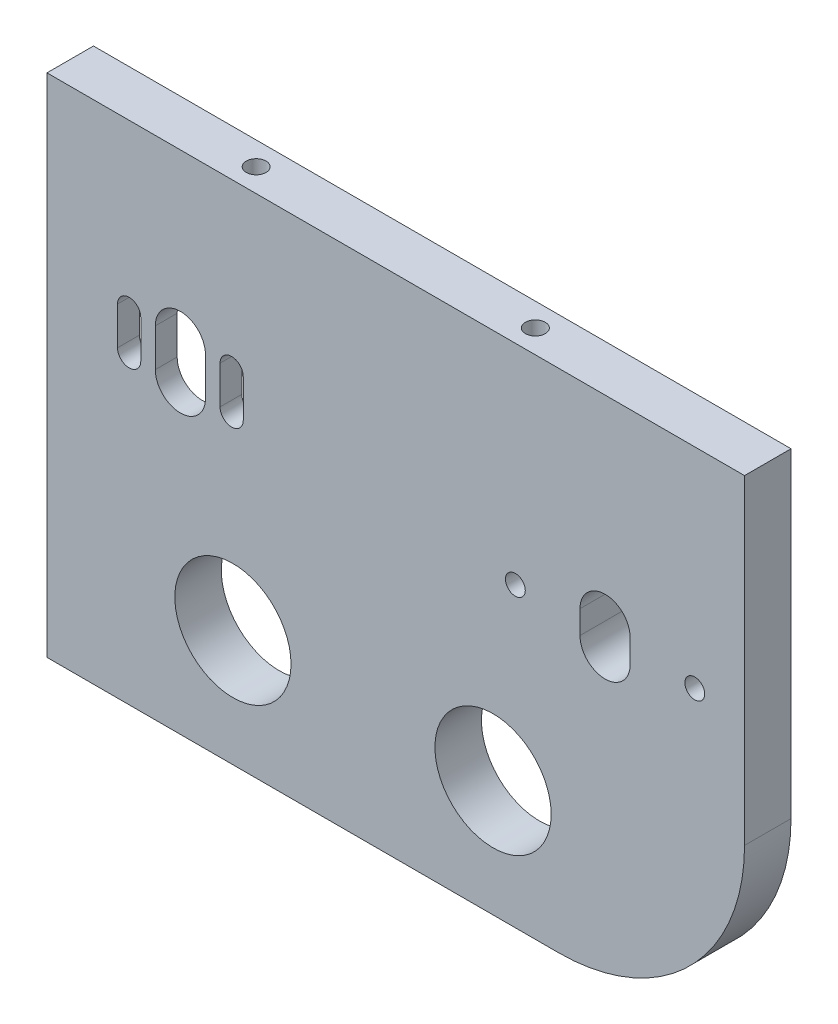
SolidWorks part; units mm, degrees
note: The reader was unsure of these and kept them because the rebuilt part matched: shared geometry of "Sketch4<3>".
ref_plane "Front Plane" through (0, 0, 0) normal (0, 0, 1) x (1, 0, 0)
ref_plane "Top Plane" through (0, 0, 0) normal (0, 1, 0) x (1, 0, 0)
ref_plane "Right Plane" through (0, 0, 0) normal (1, 0, 0) x (0, 0, -1)
sketch "Sketch1" plane through (0, 0, -6.35) normal (0, 0, 1) x (1, 0, 0)
  line L0 (-60.9331, -15.875) -> (34.3543, -15.875) construction
  line L1 (-60.9331, -15.875) -> (-60.9331, 53.2785) construction
  line L2 (34.3543, -15.875) -> (34.3543, 53.2785) construction
  line L3 (-60.9331, 53.2785) -> (34.3543, 53.2785) construction
  line L4 (-60.9331, -15.875) -> (34.3543, -15.875)
  line L5 (-60.9331, -15.875) -> (-60.9331, 53.2785)
  line L6 (34.3543, -15.875) -> (34.3543, 53.2785)
  line L7 (-60.9331, 53.2785) -> (34.3543, 53.2785)
  line L8 (11.8753, 23.116) -> (11.8753, 26.291) construction
  line L9 (18.7333, 23.116) -> (18.7333, 26.291) construction
  line L10 (11.8753, 23.116) -> (11.8753, 26.291)
  line L11 (18.7333, 23.116) -> (18.7333, 26.291)
  circle A0 centre (-35.5331, 0) radius 7.9375 construction
  circle A1 centre (0, 0) radius 7.9375 construction
  circle A3 centre (-35.5331, 0) radius 7.9375
  circle A4 centre (0, 0) radius 7.9375
  arc A6 (18.7333, 26.291) -> (11.8753, 26.291) centre (15.3043, 26.291) ccw construction
  arc A7 (11.8753, 23.116) -> (18.7333, 23.116) centre (15.3043, 23.116) ccw construction
  arc A8 (18.7333, 26.291) -> (11.8753, 26.291) centre (15.3043, 26.291) ccw
  arc A9 (11.8753, 23.116) -> (18.7333, 23.116) centre (15.3043, 23.116) ccw
extrude "Boss-Extrude1" add sketch "Sketch1" along normal blind 6.35
fillet "Fillet1" radius 25.4 1 edges at (34.3543, -15.875, -3.175)
hole_wizard "#6-32 Tapped Hole1" positions "Sketch2" profile "Sketch3" tap size "#6-32" standard "ANSI Inch"
sketch "Sketch2" plane through (0, 0, -6.35) normal (0, 0, -1) x (-1, 0, 0)
  point P0 (-27.5598, 24.7035)
  point P2 (-3.0488, 24.7035)
sketch "Sketch3" plane through (27.5598, 24.7035, -6.35) normal (1, 0, 0) x (0, 1, 0)
  line L0 (0, 0) -> (0, 11.7855)
  line L1 (0, 11.7855) -> (1.3525, 10.9728)
  line L2 (1.3525, 10.9728) -> (1.3525, 0)
  line L5 (1.3525, 0) -> (0, 0)
  line L10 (0, 11.7855) -> (-1.3526, 10.9728) construction
  line L11 (0, -6.35) -> (0, 107.95) construction
  dimension "Tap Drill Dia." = 2.7051
  dimension "Tap Drill Depth" = 10.9728
  dimension "Drill Angle" = 118
cosmetic thread "Hole Thread1" parameters "D1"=6.35, "D2"=3.5052
cosmetic thread "Hole Thread2" parameters "D1"=6.35, "D2"=3.5052
sketch "Sketch4" plane through (0, 0, -6.35) normal (0, 0, -1) x (-1, 0, 0)
  line L0 (29.6073, 30.748) -> (29.6073, 25.573) construction
  line L1 (55.8073, 30.748) -> (55.8073, 25.573) construction
  line L2 (29.6073, 30.748) -> (29.6073, 25.573)
  line L3 (55.8073, 30.748) -> (55.8073, 25.573)
  line L4 (46.1323, 30.748) -> (46.1323, 25.573) construction
  line L5 (39.2823, 30.748) -> (39.2823, 25.573) construction
  line L6 (46.1323, 30.748) -> (46.1323, 25.573)
  line L7 (39.2823, 30.748) -> (39.2823, 25.573)
  line L8 (34.1198, 30.748) -> (34.1198, 25.573) construction
  line L9 (37.2948, 30.748) -> (37.2948, 25.573) construction
  line L10 (48.1198, 30.748) -> (48.1198, 25.573) construction
  line L11 (51.2948, 30.748) -> (51.2948, 25.573) construction
  line L12 (34.1198, 30.748) -> (34.1198, 25.573)
  line L13 (37.2948, 30.748) -> (37.2948, 25.573)
  line L14 (48.1198, 30.748) -> (48.1198, 25.573)
  line L15 (51.2948, 30.748) -> (51.2948, 25.573)
  arc A0 (29.6073, 25.573) -> (55.8073, 25.573) centre (42.7073, 25.573) ccw construction
  arc A1 (55.8073, 30.748) -> (29.6073, 30.748) centre (42.7073, 30.748) ccw construction
  arc A2 (29.6073, 25.573) -> (55.8073, 25.573) centre (42.7073, 25.573) ccw
  arc A3 (55.8073, 30.748) -> (29.6073, 30.748) centre (42.7073, 30.748) ccw
  arc A4 (46.1323, 30.748) -> (39.2823, 30.748) centre (42.7073, 30.748) ccw construction
  arc A5 (39.2823, 25.573) -> (46.1323, 25.573) centre (42.7073, 25.573) ccw construction
  arc A6 (46.1323, 30.748) -> (39.2823, 30.748) centre (42.7073, 30.748) ccw
  arc A7 (39.2823, 25.573) -> (46.1323, 25.573) centre (42.7073, 25.573) ccw
  arc A8 (34.1198, 25.573) -> (37.2948, 25.573) centre (35.7073, 25.573) ccw construction
  arc A9 (37.2948, 30.748) -> (34.1198, 30.748) centre (35.7073, 30.748) ccw construction
  arc A10 (51.2948, 30.748) -> (48.1198, 30.748) centre (49.7073, 30.748) ccw construction
  arc A11 (48.1198, 25.573) -> (51.2948, 25.573) centre (49.7073, 25.573) ccw construction
  arc A12 (34.1198, 25.573) -> (37.2948, 25.573) centre (35.7073, 25.573) ccw
  arc A13 (37.2948, 30.748) -> (34.1198, 30.748) centre (35.7073, 30.748) ccw
  arc A14 (51.2948, 30.748) -> (48.1198, 30.748) centre (49.7073, 30.748) ccw
  arc A15 (48.1198, 25.573) -> (51.2948, 25.573) centre (49.7073, 25.573) ccw
extrude "Cut-Extrude2" cut sketch "Sketch4<3>" against normal through all contours L7 A7 L6 A6 | L14 A15 L15 A14 | L13 A13 L12 A12
sketch "Sketch4<3>" plane through (0, 0, -6.35) normal (0, 0, -1) x (-1, 0, 0) same geometry as "Sketch4"
extrude "Cut-Extrude1" cut sketch "Sketch4" against normal up to vertex (3.367 mm away)
hole_wizard "#6-32 Tapped Hole2" positions "Sketch5" profile "Sketch6" tap size "#6-32" standard "ANSI Inch"
sketch "Sketch5" plane through (0, 53.2785, 0) normal (0, 1, 0) x (1, 0, 0)
  line L0 (-60.9331, 3.175) -> (34.3543, 3.175) construction
  line L1 (-60.9331, 0) -> (-60.9331, 6.35) construction
  line L2 (34.3543, 0) -> (34.3543, 6.35) construction
  point P0 (-35.5331, 3.175)
  point P2 (2.6043, 3.175)
  dimension "D1" = 31.75
  dimension "D2" = 25.4
sketch "Sketch6" plane through (-35.5331, 53.2785, -3.175) normal (1, 0, 0) x (0, 0, 1)
  line L0 (0, 0) -> (0, 10.2107)
  line L1 (0, 10.2107) -> (1.3525, 9.398)
  line L2 (1.3525, 9.398) -> (1.3525, 0)
  line L5 (1.3525, 0) -> (0, 0)
  line L10 (0, 10.2107) -> (-1.3525, 9.398) construction
  line L11 (0, -6.35) -> (0, 107.95) construction
  dimension "Tap Drill Dia." = 2.7051
  dimension "Tap Drill Depth" = 9.398
  dimension "Drill Angle" = 118
cosmetic thread "Hole Thread3"
cosmetic thread "Hole Thread4"
hole_wizard "#6-32 Tapped Hole3" positions "Sketch7" profile "Sketch8" tap size "#6-32" standard "ANSI Inch"
sketch "Sketch7" plane through (-60.9331, 0, 0) normal (-1, 0, 0) x (0, 0, 1)
  line L0 (-3.175, -15.875) -> (-3.175, 53.2785) construction
  line L1 (0, -15.875) -> (-6.35, -15.875) construction
  line L2 (0, 53.2785) -> (-6.35, 53.2785) construction
  point P0 (-3.175, 6.35)
  point P2 (-3.175, 45.341)
  dimension "D1" = 7.9375
  dimension "D2" = 22.225
sketch "Sketch8" plane through (-60.9331, 6.35, -3.175) normal (0, 1, 0) x (0, 0, 1)
  line L0 (0, 0) -> (0, 10.2107)
  line L1 (0, 10.2107) -> (1.3525, 9.398)
  line L2 (1.3525, 9.398) -> (1.3525, 0)
  line L5 (1.3525, 0) -> (0, 0)
  line L10 (0, 10.2107) -> (-1.3525, 9.398) construction
  line L11 (0, -6.35) -> (0, 107.95) construction
  dimension "Tap Drill Dia." = 2.7051
  dimension "Tap Drill Depth" = 9.398
  dimension "Drill Angle" = 118
cosmetic thread "Hole Thread5"
cosmetic thread "Hole Thread6"
